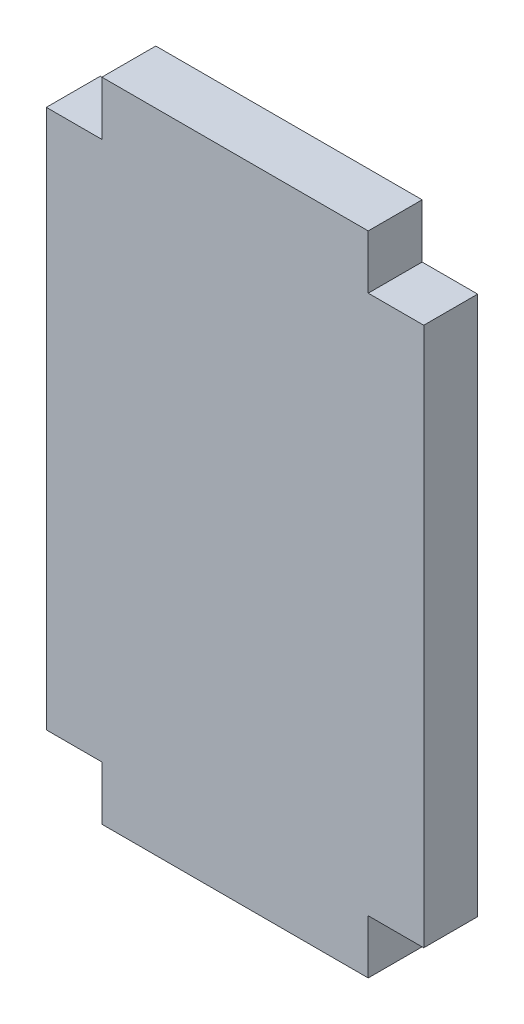
SolidWorks part; units mm, degrees
ref_plane "Front Plane" through (0, 0, 0) normal (0, 0, 1) x (1, 0, 0)
ref_plane "Top Plane" through (0, 0, 0) normal (0, 1, 0) x (1, 0, 0)
ref_plane "Right Plane" through (0, 0, 0) normal (1, 0, 0) x (0, 0, -1)
sketch "Sketch1" plane through (0, 0, 0) normal (0, 0, 1) x (1, 0, 0)
  line L1 (-17.5, 50) -> (17.5, 50)
  line L2 (-17.5, 50) -> (-17.5, 0)
  line L3 (-17.5, 0) -> (17.5, 0)
  line L4 (17.5, 50) -> (17.5, 0)
  point P4 (0, 0)
  dimension "D1" = 50
  dimension "D2" = 35
extrude "Boss-Extrude1" add sketch "Sketch1" along normal blind 5
sketch "Sketch2" plane through (0, 50, 0) normal (0, 1, 0) x (1, 0, 0)
  line L0 (17.5, 0) -> (-17.5, 0) construction
  line L1 (-12.35, 0) -> (12.35, 0)
  line L2 (-12.35, 0) -> (-12.35, -5)
  line L3 (-12.35, -5) -> (12.35, -5)
  line L4 (12.35, 0) -> (12.35, -5)
  line L5 (17.5, -5) -> (-17.5, -5) construction
  point P8 (0, 0)
  dimension "D1" = 24.7
extrude "Boss-Extrude2" add sketch "Sketch2" along normal blind 5
extrude "Boss-Extrude3" add sketch "Sketch2<2>" against normal blind 55
sketch "Sketch2<2>" plane through (0, 50, 0) normal (0, 1, 0) x (1, 0, 0) same geometry as "Sketch2"
